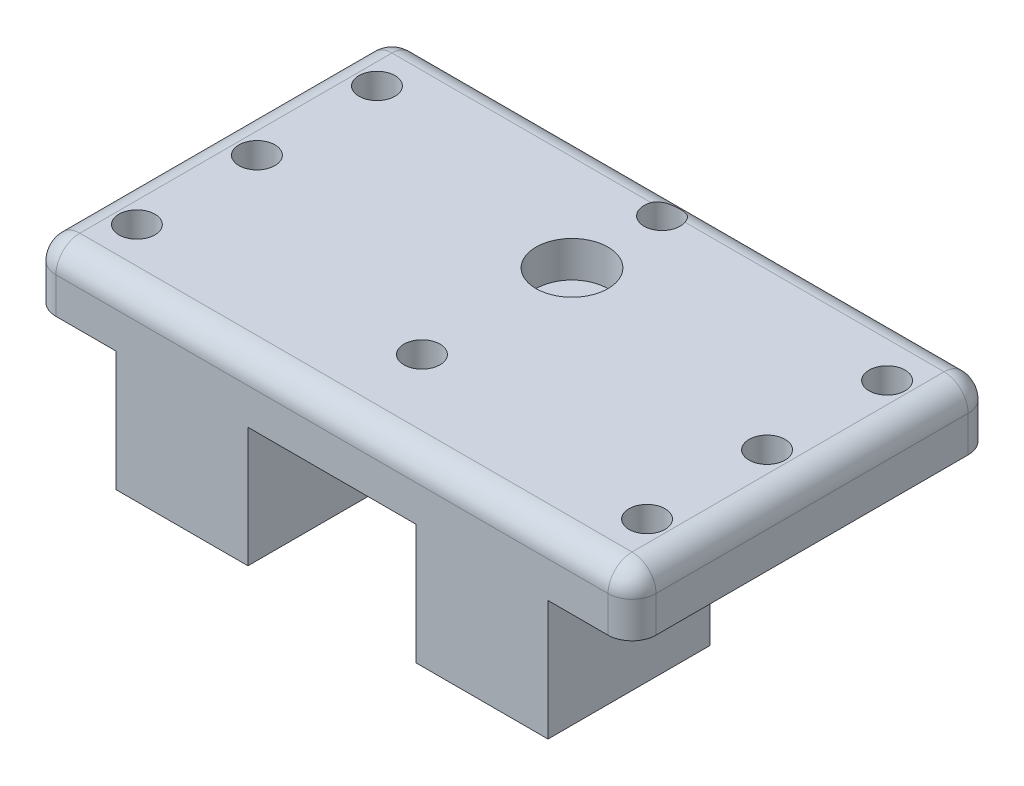
SolidWorks part; units mm, degrees
material "ABS"
ref_plane "Спереди" through (0, 0, 0) normal (0, 0, 1) x (1, 0, 0)
ref_plane "Сверху" through (0, 0, 0) normal (0, 1, 0) x (1, 0, 0)
ref_plane "Справа" through (0, 0, 0) normal (1, 0, 0) x (0, 0, -1)
sketch "Эскиз1" plane through (0, 0, 0) normal (0, 1, 0) x (1, 0, 0)
  line L1 (25, -15) -> (-25, -15)
  line L2 (25, -15) -> (25, 15)
  line L3 (25, 15) -> (-25, 15)
  line L4 (-25, -15) -> (-25, 15)
  line L5 (25, -15) -> (-25, 15) construction
  line L6 (25, 15) -> (-25, -15) construction
  point P0 (0, 0)
  dimension "D1" = 50
  dimension "D2" = 30
extrude "Бобышка-Вытянуть1" add sketch "Эскиз1" along normal blind 5
sketch "Эскиз2" plane through (0, 5, 0) normal (0, 1, 0) x (1, 0, 0)
  circle A0 centre (0, 5) radius 1.25
extrude "Вырез-Вытянуть1" cut sketch "Эскиз2" against normal through all
sketch "Эскиз3" plane through (0, 0, 0) normal (0, -1, 0) x (1, 0, 0)
  circle A0 centre (-21.25, 0) radius 1.5
  circle A1 centre (0, 7.5) radius 1.5
  circle A2 centre (21.25, 0) radius 1.5
  circle A3 centre (0, -12.5) radius 1.5
extrude "Вырез-Вытянуть2" cut sketch "Эскиз3" against normal through all
sketch "Эскиз4" plane through (0, 0, 0) normal (0, -1, 0) x (1, 0, 0)
  line L3 (-7, 15) -> (-18, 15)
  line L5 (-7, 1.5) -> (-7, 15)
  line L7 (-18, 1.5) -> (-18, 15)
  line L8 (-7, 1.5) -> (-18, 1.5)
  line L9 (-18, 1.5) -> (-18, 14.5) construction
  line L10 (-7, 1.5) -> (-7, 14.5) construction
  line L11 (-18.5, 1) -> (-18.5, 15) construction
  line L12 (-6.5, 1) -> (-18.5, 1) construction
  line L13 (-6.5, 1) -> (-6.5, 15) construction
  line L14 (-7, 14.5) -> (-18, 14.5) construction
  line L15 (-6.5, 15) -> (-18.5, 15) construction
  line L16 (0, 0) -> (0, 21.2006) construction
  line L17 (7, 1.5) -> (18, 1.5)
  line L18 (18, 1.5) -> (18, 15)
  line L19 (7, 1.5) -> (7, 15)
  line L20 (7, 15) -> (18, 15)
  dimension "D1" = 0.5
extrude "Бобышка-Вытянуть2" add sketch "Эскиз4" along normal blind 10
sketch "Эскиз5" plane through (0, 5, 0) normal (0, 1, 0) x (1, 0, 0)
  line L0 (-21.25, 0) -> (-21.25, -15) construction
  line L1 (-25, -15) -> (25, -15) construction
  line L2 (-25, -15) -> (-16.2321, -15) construction
  line L3 (-25, -10) -> (-16.2321, -10) construction
  line L4 (0, 0) -> (0, 8.2638) construction
  line L5 (0, 0) -> (-10.9542, 0) construction
  circle A0 centre (-21.25, -10) radius 1.5
  circle A1 centre (-21.25, 10) radius 1.5
  circle A2 centre (21.25, -10) radius 1.5
  circle A3 centre (21.25, 10) radius 1.5
  dimension "D1" = 5
extrude "Вырез-Вытянуть3" cut sketch "Эскиз5" against normal through all
fillet "Скругление1" radius 2 8 edges at (25, 5, 0) (0, 5, -15) (-25, 5, 0) (-25, 2.5, -15) (-25, 2.5, 15) (0, 5, 15) (25, 2.5, 15) (25, 2.5, -15)
sketch "Эскиз6" plane through (0, 5, 0) normal (0, 1, 0) x (1, 0, 0)
  circle A0 centre (0, 5) radius 3
extrude "Вырез-Вытянуть4" cut sketch "Эскиз6" against normal blind 3
